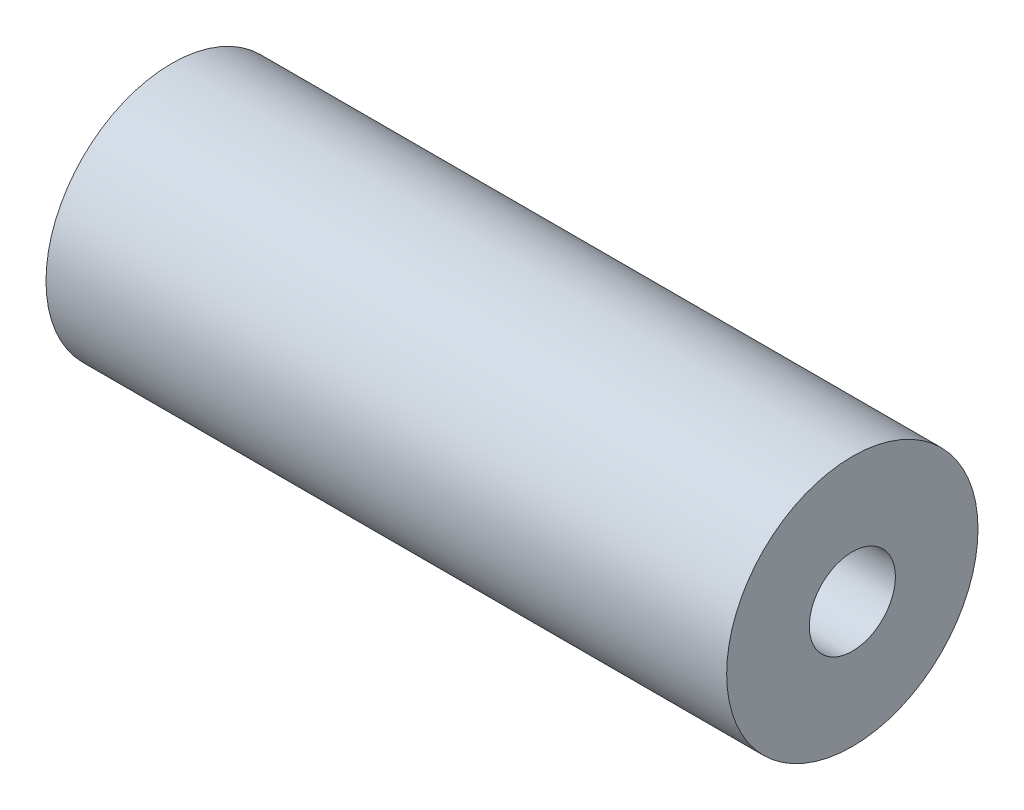
SolidWorks part; units mm, degrees
material "ABS"
ref_plane "Front Plane" through (0, 0, 0) normal (0, 0, 1) x (1, 0, 0)
ref_plane "Top Plane" through (0, 0, 0) normal (0, 1, 0) x (1, 0, 0)
ref_plane "Right Plane" through (0, 0, 0) normal (1, 0, 0) x (0, 0, -1)
sketch "Sketch1" plane through (0, 0, 0) normal (1, 0, 0) x (0, 0, -1)
  circle A0 centre (0, 0) radius 9.525
  circle A1 centre (0, 0) radius 3.2639
  dimension "D1" = 19.05
  dimension "D2" = 6.5278
extrude "Boss-Extrude1" add sketch "Sketch1" along normal blind 51.5938
